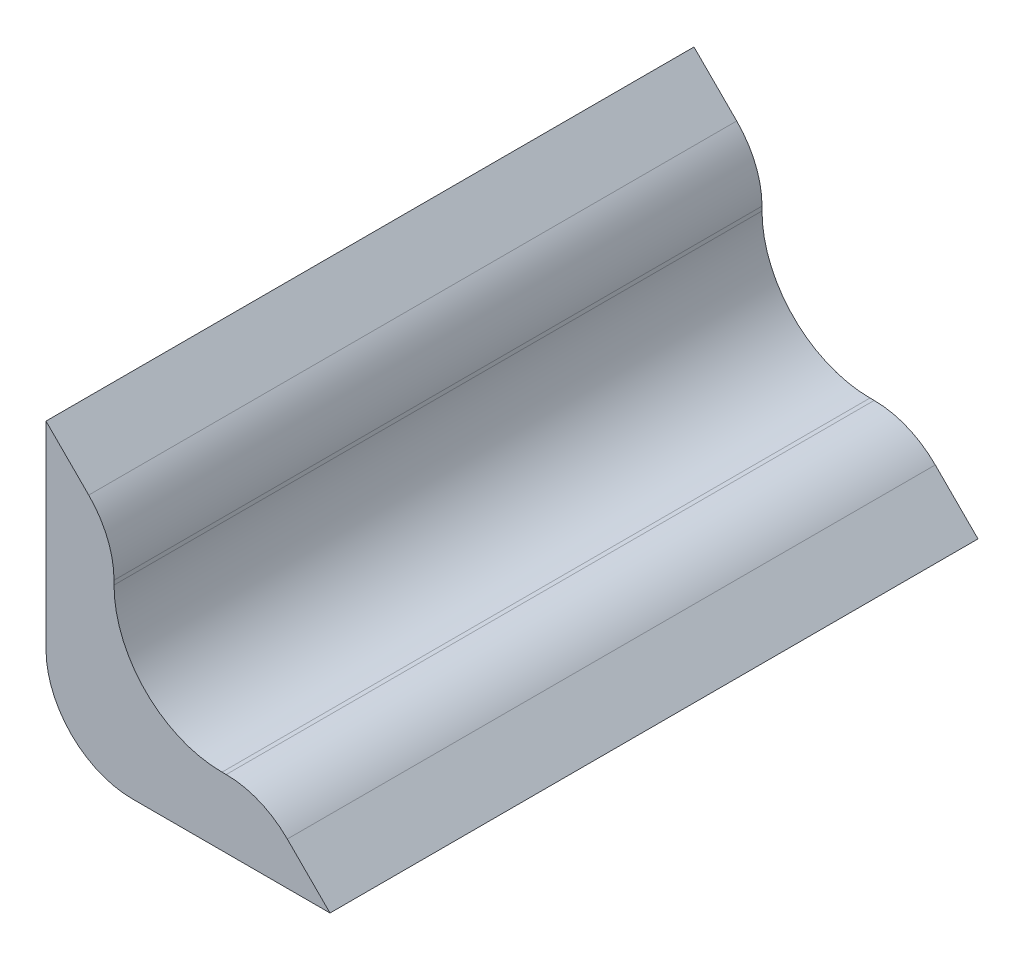
SolidWorks part; units mm, degrees
ref_plane "Front Plane" through (0, 0, 0) normal (0, 0, 1) x (1, 0, 0)
ref_plane "Top Plane" through (0, 0, 0) normal (0, 1, 0) x (1, 0, 0)
ref_plane "Right Plane" through (0, 0, 0) normal (1, 0, 0) x (0, 0, -1)
sketch "Sketch1" plane through (0, 0, 0) normal (0, 0, 1) x (1, 0, 0)
  line L0 (0, 0) -> (8.35, 0)
  line L1 (8.35, 0) -> (8.35, 2)
  line L2 (8.35, 2) -> (2, 2)
  line L3 (2, 2) -> (2, 8.35)
  line L4 (2, 8.35) -> (0, 8.35)
  line L5 (0, 8.35) -> (0, 0)
  dimension "D1" = 6.35
  dimension "D2" = 6.35
  dimension "D3" = 2
  dimension "D4" = 2
extrude "Boss-Extrude1" add sketch "Sketch1" along normal mid plane 19.05
chamfer "Chamfer1" distance 2 angle 45 2 edges at (8.35, 2, 0) (2, 8.35, 0)
fillet "Fillet1" radius 2.54 2 edges at (6.35, 2, 0) (2, 6.35, 0)
fillet "Fillet2" radius 2.54 1 edges at (0, 0, 0)
fillet "Fillet3" radius 3.175 1 edges at (2, 2, 0)
